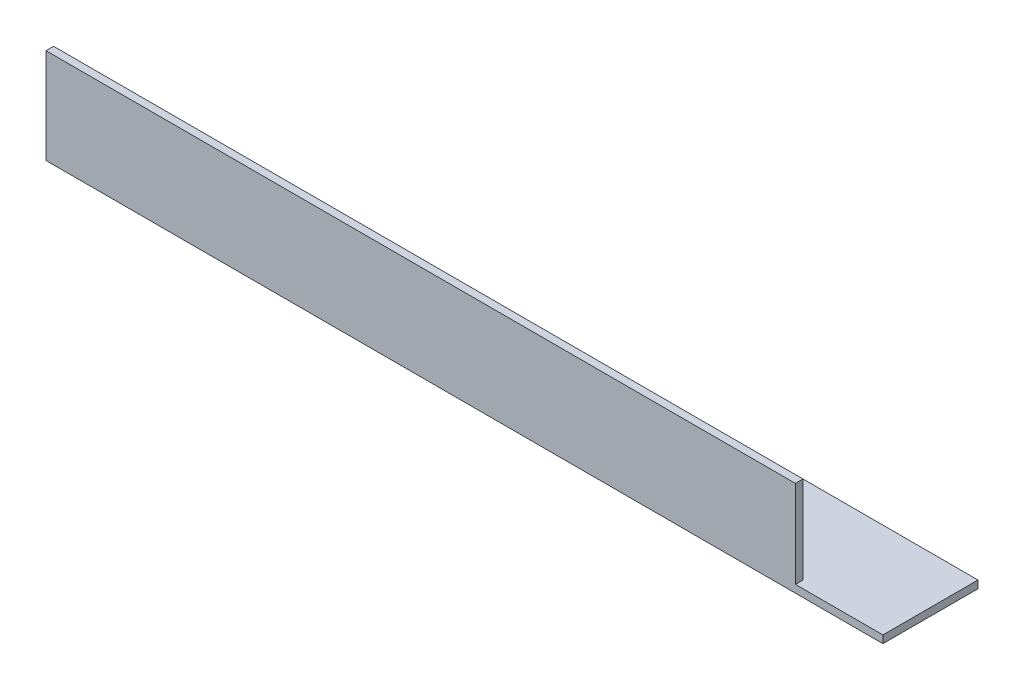
SolidWorks part; units mm, degrees
ref_plane "Спереди" through (0, 0, 0) normal (0, 0, 1) x (1, 0, 0)
ref_plane "Сверху" through (0, 0, 0) normal (0, 1, 0) x (1, 0, 0)
ref_plane "Справа" through (0, 0, 0) normal (1, 0, 0) x (0, 0, -1)
sketch "Эскиз1" plane through (0, 0, 0) normal (1, 0, 0) x (0, 0, -1)
  line L0 (0, 25) -> (0, 0)
  line L1 (0, 0) -> (25, 0)
extrude "Вытянуть-Тонкостенный1" add sketch "Эскиз1" along normal blind 220 thin thin type one direction reverse wall 2
sketch "Эскиз3" plane through (0, 0, 0) normal (0, 0, 1) x (1, 0, 0)
  line L1 (197, 2) -> (220, 2)
  line L2 (197, 2) -> (197, 25)
  line L3 (197, 25) -> (220, 25)
  line L4 (220, 2) -> (220, 25)
  dimension "D1" = 23
extrude "Вырез-Вытянуть1" cut sketch "Эскиз3" against normal through all
